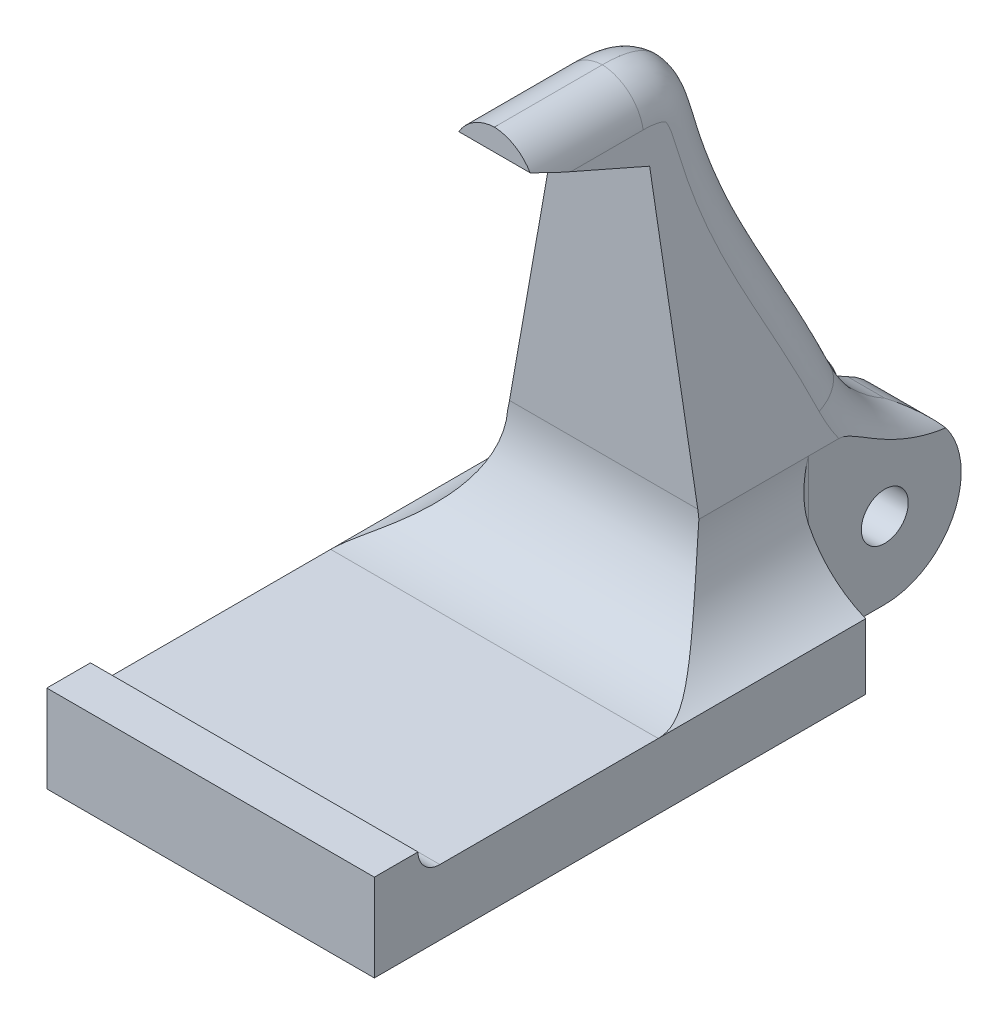
SolidWorks part; units mm, degrees
ref_plane "Front Plane" through (0, 0, 0) normal (0, 0, 1) x (1, 0, 0)
ref_plane "Top Plane" through (0, 0, 0) normal (0, 1, 0) x (1, 0, 0)
ref_plane "Right Plane" through (0, 0, 0) normal (1, 0, 0) x (0, 0, -1)
sketch "Sketch1" plane through (0, 0, 0) normal (0, 1, 0) x (1, 0, 0)
  line L0 (0, -64.9732) -> (0, 0) construction
  line L1 (-8.75, 0) -> (8.75, 0)
  line L2 (8.75, 0) -> (8.75, -15)
  line L3 (8.75, -15) -> (15, -15)
  line L4 (15, -15) -> (15, -60)
  line L5 (15, -60) -> (-15, -60)
  line L6 (-15, -15) -> (-15, -60)
  line L7 (-8.75, -15) -> (-15, -15)
  line L8 (-8.75, 0) -> (-8.75, -15)
  point P13 (0, -60)
  dimension "D1" = 30
  dimension "D2" = 45
  dimension "D3" = 15
  dimension "D4" = 17.5
extrude "Boss-Extrude1" add sketch "Sketch1" along normal blind 6
sketch "Sketch3" plane through (-8.75, 0, 0) normal (-1, 0, 0) x (0, 0, 1)
  line L10 (14, 6) -> (14, 7)
  line L11 (0, 7) -> (0, 6)
  line L12 (0, 0) -> (15, 0) construction
  line L13 (14, 6) -> (0, 6)
  line L14 (0, 6) -> (15, 6) construction
  arc A0 (14, 7) -> (0, 7) centre (7, 7) ccw
  dimension "D2" = 7
  dimension "D1" = 7
extrude "Boss-Extrude2" add sketch "Sketch3" against normal up to surface (17.5 mm away) up to face at (8.75, 3, 7.5)
sketch "Sketch5" plane through (-8.75, 0, 0) normal (-1, 0, 0) x (0, 0, 1)
  line L0 (7, 14) -> (7, 0) construction
  line L1 (0, 0) -> (15, 0) construction
  arc A0 (14, 7) -> (0, 7) centre (7, 7) ccw construction
  circle A1 centre (7, 7) radius 2.15
  dimension "D1" = 4.3
  dimension "D2" = 7
extrude "Cut-Extrude1" cut sketch "Sketch5" against normal up to surface (17.5 mm away) up to face at (8.75, 5.5, 9.6667)
fillet "Fillet1" radius 7 1 edges at (0, 0, 0)
sketch "Sketch6" plane through (0, 6, 0) normal (0, 1, 0) x (1, 0, 0)
  line L0 (0, -60) -> (0, 0) construction
  line L1 (-15, -60) -> (15, -60) construction
  line L2 (8.75, 0) -> (-8.75, 0) construction
  line L3 (2.25, -15) -> (-2.25, -15)
  line L4 (2.25, -15) -> (2.25, 0)
  line L5 (2.25, 0) -> (-2.25, 0)
  line L6 (-2.25, -15) -> (-2.25, 0)
  line L7 (2.25, -15) -> (-2.25, 0) construction
  line L8 (2.25, 0) -> (-2.25, -15) construction
  line L10 (8.75, -15) -> (-8.75, -15) construction
  point P5 (0, -7.5)
  dimension "D1" = 4.5
extrude "Cut-Extrude3" cut sketch "Sketch6" along normal blind 8 and the other way blind 8
sketch "Sketch7" plane through (8.75, 0, 0) normal (1, 0, 0) x (0, 0, -1)
  line L0 (-24, 6) -> (-24, 41)
  line L1 (-60, 6) -> (-15, 6) construction
  line L2 (-24, 41) -> (-34, 41)
  line L3 (-34, 41) -> (-34, 47)
  line L4 (-34, 47) -> (-24.1105, 47)
  line L6 (-14, 6) -> (-14, 7)
  line L8 (-24, 6) -> (-14, 6)
  line L10 (-19.2414, 47) -> (-2.1273, 47) construction
  arc A0 (-14, 7) -> (-7.1795, 13.9977) centre (-7, 7) cw
  circle A3 centre (-7, 7) radius 2.15 construction
  circle A4 centre (-7, 7) radius 2.15 construction
  arc A6 (0, 7) -> (-14, 7) centre (-7, 7) ccw construction
  spline S0 degree 3 poles (-24.1105, 47) (-18.2212, 47) (-17.2286, 32.8523) (-10.9379, 25.6757) (-7.1795, 13.9977) knots 0 0 0 0 0.25089 1 1 1 1
  point P8 (-17.3897, 40.3398)
  dimension "D5" = 0
  dimension "D1" = 10
  dimension "D2" = 35
  dimension "D3" = 6
  dimension "D4" = 10
extrude "Boss-Extrude3" add sketch "Sketch7" against normal up to surface (17.5 mm away) up to face at (-8.75, 7, 9.15)
sketch "Sketch8" plane through (-2.25, 0, 0) normal (1, 0, 0) x (0, 0, -1)
  line L3 (-15, 6) -> (-15, 7)
  line L5 (-7, 15) -> (-7, 7)
  line L6 (-15, 6) -> (-7, 6)
  line L7 (-7, 6) -> (-7, 7)
  arc A0 (-15, 7) -> (-7, 15) centre (-7, 7) cw
extrude "Cut-Extrude4" cut sketch "Sketch8" along normal up to surface (4.5 mm away) up to face at (2.25, 5.9213, 10.0967)
fillet "Fillet3" radius 10 3 edges at (0, 6, 24) (8.75, 6, 19.5) (-8.75, 6, 19.5)
fillet "Fillet6" radius 1 2 edges at (8.75, 7.6351, 15) (-8.75, 7.6351, 15)
fillet "Fillet7" radius 10 1 edges at (5.5, 13.9977, 7.1795)
ref_plane "Plane1" through (-11.0975, 1.9568, 0) normal (0.9848, -0.1736, 0) x (0, 0, 1)
sketch "Sketch9" plane through (-11.0975, 1.9568, 0) normal (0.9848, -0.1736, 0) x (0, 0, 1)
  line L1 (6.3535, -13.5188) -> (38.0706, -13.5188)
  line L2 (6.3535, -13.5188) -> (6.3535, -53.3281)
  line L3 (6.3535, -53.3281) -> (38.0706, -53.3281)
  line L4 (38.0706, -13.5188) -> (38.0706, -53.3281)
extrude "Cut-Extrude5" cut sketch "Sketch9" against normal blind 10
mirror "Mirror1" about plane through (0, 0, 0) normal (1, 0, 0) of "Cut-Extrude5"
sketch "Sketch10" plane through (15, 0, 0) normal (1, 0, 0) x (0, 0, -1)
  line L0 (-60, 6) -> (-60, 8)
  line L1 (-60, 8) -> (-56, 8)
  line L2 (-56, 8) -> (-56, 6)
  line L3 (-60, 6) -> (-34, 6) construction
  line L4 (-56, 6) -> (-60, 6)
  dimension "D1" = 4
  dimension "D2" = 2
extrude "Boss-Extrude4" add sketch "Sketch10" against normal up to surface (30 mm away) up to face at (-15, 3.6, 36.8)
fillet "Fillet8" radius 2 1 edges at (0, 6, 56)
chamfer "Chamfer1" distance 10 distance2 4 1 edges at (0, 41, 34) first distance on face at (0, 41, 29)
fillet "Fillet9" radius 4 6 edges at (8.474, 16.8357, 7.9131) (3.6264, 44.3277, 18.4562) (-8.474, 16.8357, 7.9131) (-3.5401, 44.8169, 18.7468) (3.1552, 47, 29.0552) (-3.1552, 47, 29.0552)
